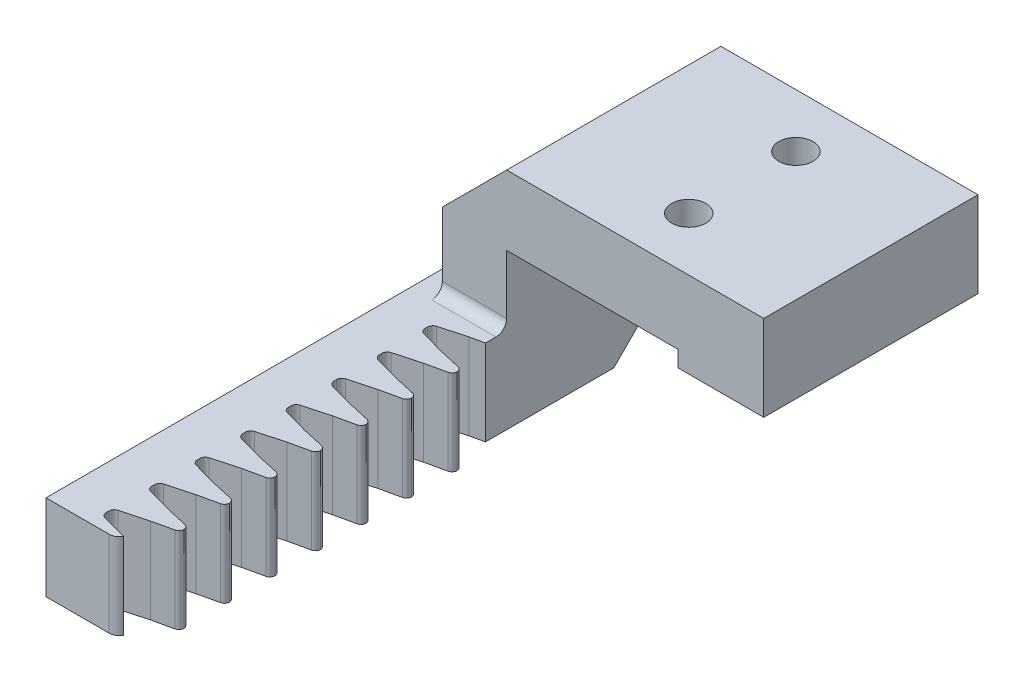
SolidWorks part; units mm, degrees
ref_plane "Front Plane" through (0, 0, 0) normal (0, 0, 1) x (1, 0, 0)
ref_plane "Top Plane" through (0, 0, 0) normal (0, 1, 0) x (1, 0, 0)
ref_plane "Right Plane" through (0, 0, 0) normal (1, 0, 0) x (0, 0, -1)
sketch "Sketch1" plane through (0, 0, 0) normal (0, 0, 1) x (1, 0, 0)
  line L1 (0, 0) -> (30, 0)
  line L2 (0, 0) -> (0, -16)
  line L3 (0, -16) -> (30, -16)
  line L4 (30, 0) -> (30, -16)
  dimension "D1" = 30
  dimension "D2" = 16
extrude "Boss-Extrude1" add sketch "Sketch1" along normal blind 20
sketch "Sketch2" plane through (0, 0, 20) normal (0, 0, 1) x (1, 0, 0)
  line L0 (22, -6.5) -> (22, -8)
  line L7 (6, -16) -> (6, -6.5)
  line L8 (6, -6.5) -> (22, -6.5)
  line L14 (22, -8) -> (30, -8)
  line L15 (30, -16) -> (30, 0) construction
  line L16 (30, -8) -> (30, -16)
  line L17 (30, -16) -> (6, -16)
  dimension "D1" = 24
  dimension "D2" = 8
  dimension "D7" = 16
extrude "Cut-Extrude1" cut sketch "Sketch2" against normal up to surface (20 mm away) contours L8 L0 L14 L16 L17 L7 up to face at (15, -8, 0)
sketch "Sketch3" plane through (0, -16, 0) normal (0, -1, 0) x (1, 0, 0)
  line L0 (0, 20) -> (0, 0) construction
  line L1 (0, 15) -> (6, 15)
  line L2 (0, 15) -> (0, 5)
  line L3 (0, 5) -> (6, 5)
  line L4 (6, 15) -> (6, 5)
  line L6 (0, 20) -> (6, 20) construction
  dimension "D1" = 5
  dimension "D2" = 10
  dimension "D3" = 6
extrude "Boss-Extrude2" add sketch "Sketch3" along normal blind 5
ref_plane "Plane1" through (0, 0, 0) normal (-1, 0, 0) x (0, 0, 1)
sketch "Sketch9" plane through (0, -6.5, 0) normal (0, -1, 0) x (1, 0, 0)
  line L0 (30, 0) -> (30, 20) construction
  line L3 (6, 20) -> (22, 20) construction
  circle A0 centre (18, 15) radius 1.6
  circle A1 centre (18, 5) radius 1.6
  dimension "D1" = 3.2
  dimension "D2" = 3.2
  dimension "D3" = 12
  dimension "D4" = 12
  dimension "D5" = 10
  dimension "D6" = 5
extrude "Cut-Extrude3" cut sketch "Sketch9" against normal up to surface (6.5 mm away) up to face at (15, 0, 10)
sketch "Sketch11" plane through (0, 0, 15) normal (0, 0, 1) x (1, 0, 0)
  line L0 (6, -21) -> (0, -21) construction
  line L1 (-2, -13) -> (8, -13)
  line L2 (-2, -13) -> (-2, -21)
  line L3 (-2, -21) -> (8, -21)
  line L4 (8, -13) -> (8, -21)
  line L5 (0, -21) -> (0, -16) construction
  line L6 (6, -21) -> (6, -16) construction
  dimension "D1" = 2
  dimension "D2" = 2
  dimension "D3" = 8
extrude "Boss-Extrude4" add sketch "Sketch11" along normal blind 40
chamfer "Chamfer2" distance 2 distance2 10 1 edges
fillet "Fillet1" radius 1 1 edges at (3, -13, 20)
sketch "Sketch12" plane through (0, -21, 0) normal (0, -1, 0) x (1, 0, 0)
  line L0 (7, 55) -> (4.75, 54.5)
  line L1 (4.75, 54.5) -> (2, 53.75)
  line L3 (2, 53.25) -> (8, 53.25) construction
  line L4 (8, 55) -> (8, 15) construction
  line L7 (2, 55) -> (2, 48) construction
  line L8 (-2, 55) -> (8, 55) construction
  line L14 (2, 53.75) -> (2, 52.75)
  line L15 (4.75, 52) -> (2, 52.75)
  line L16 (7, 51.5) -> (4.75, 52)
  line L17 (7, 55) -> (8, 55)
  line L18 (7, 51.5) -> (7, 50.75)
  line L19 (7, 50.75) -> (8, 50.75)
  line L20 (8, 50.75) -> (8, 55)
  dimension "D1" = 0.5
  dimension "D2" = 0.75
  dimension "D3" = 2.25
  dimension "D4" = 1
  dimension "D5" = 0.5
  dimension "D6" = 6
  dimension "D7" = 0.75
extrude "Cut-Extrude4" cut sketch "Sketch12" against normal blind 8
sketch "Sketch13" plane through (0, 0, 15) normal (0, 0, -1) x (-1, 0, 0)
  line L0 (-6, -21) -> (-8, -21) construction
  line L1 (-8, -13) -> (-6, -13)
  line L2 (-8, -13) -> (-8, -21)
  line L3 (-8, -21) -> (-6, -21)
  line L4 (-6, -13) -> (-6, -21)
extrude "Boss-Extrude5" add sketch "Sketch13" along normal blind 10
pattern_linear "LPattern1" count 8 spacing 4.25 along (0, 0, -1) of "Cut-Extrude4"
fillet "Fillet2" radius 0.5 30 edges at (2, -17, 52.75) (2, -17, 53.75) (2, -17, 48.5) (2, -17, 49.5) (2, -17, 44.25) (2, -17, 45.25) (2, -17, 35.75) (2, -17, 36.75) (2, -17, 40) (2, -17, 41) (7, -17, 33.75) (7, -17, 34.5) (7, -17, 38) (7, -17, 38.75) (7, -17, 42.25) (7, -17, 43) (7, -17, 46.5) (7, -17, 47.25) (7, -17, 50.75) (7, -17, 51.5) (7, -17, 25.25) (7, -17, 26) (7, -17, 29.5) (7, -17, 30.25) (2, -17, 23) (2, -17, 24) (2, -17, 27.25) (2, -17, 28.25) (2, -17, 32.5) (2, -17, 31.5)
fillet "Fillet3" radius 1 1 edges at (7, -17, 55)
sketch "Sketch14" plane through (0, 0, 5) normal (0, 0, -1) x (-1, 0, 0)
  line L1 (-6, -13) -> (-8, -13)
  line L2 (-6, -13) -> (-6, -21)
  line L3 (-6, -21) -> (-8, -21)
  line L4 (-8, -13) -> (-8, -21)
extrude "Cut-Extrude5" cut sketch "Sketch14" against normal blind 17
chamfer "Chamfer3" distance 6 angle 45 1 edges at (0, 0, 10)
chamfer "Chamfer4" distance 5 angle 45 3 edges at (3, -21, 5) (3, -16, 0)
